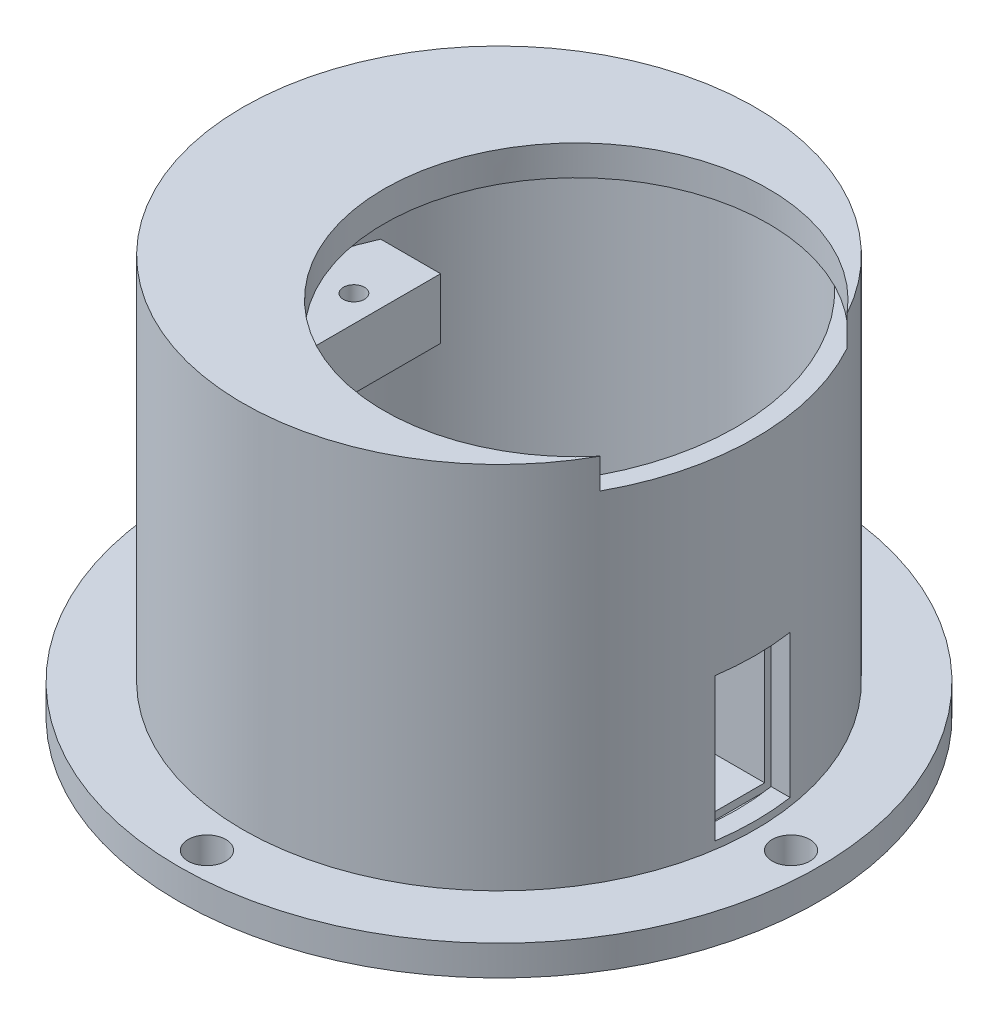
SolidWorks part; units mm, degrees
ref_plane "Front Plane" through (0, 0, 0) normal (0, 0, 1) x (1, 0, 0)
ref_plane "Top Plane" through (0, 0, 0) normal (0, 1, 0) x (1, 0, 0)
ref_plane "Right Plane" through (0, 0, 0) normal (1, 0, 0) x (0, 0, -1)
sketch "Sketch1" plane through (0, 0, 0) normal (0, 1, 0) x (1, 0, 0)
  circle A0 centre (0, 0) radius 30
  circle A1 centre (0, 0) radius 42.5
  dimension "D1" = 60
  dimension "D2" = 85
extrude "Boss-Extrude1" add sketch "Sketch1" along normal blind 4
sketch "Sketch2" plane through (0, 4, 0) normal (0, 1, 0) x (1, 0, 0)
  circle A3 centre (0, 0) radius 34
  circle A6 centre (0, 0) radius 31.5
  dimension "D1" = 63
extrude "Boss-Extrude2" add sketch "Sketch2" along normal blind 45
sketch "Sketch3" plane through (0, 0, 0) normal (0, 0, 1) x (1, 0, 0)
  line L0 (0, 0) -> (0, 49) construction
  line L1 (34, 49) -> (-34, 49) construction
  line L2 (-42.5, 0) -> (42.5, 0) construction
  line L3 (22.25, 0) -> (30.25, 0)
  line L4 (22.25, 0) -> (22.25, 34)
  line L5 (22.25, 34) -> (30.25, 34)
  line L6 (30.25, 0) -> (30.25, 34)
  line L8 (42.5, 4) -> (-42.5, 4) construction
  line L9 (-31.25, 34) -> (-20.75, 34)
  line L10 (-31.25, 34) -> (-31.25, 26)
  line L11 (-31.25, 26) -> (-20.75, 26)
  line L12 (-20.75, 34) -> (-20.75, 26)
  point P17 (0, 0)
  point P19 (-34, 38)
  dimension "D1" = 8
  dimension "D2" = 22.25
  dimension "D3" = 30
  dimension "D4" = 22
  dimension "D5" = 8
  dimension "D6" = 20.75
  dimension "D7" = 10.5
extrude "Boss-Extrude3" add sketch "Sketch3" along normal mid plane 26
sketch "Sketch4" plane through (22.25, 0, 0) normal (-1, 0, 0) x (0, 0, 1)
  line L0 (0, 0) -> (0, 34) construction
  line L1 (13, 0) -> (-13, 0) construction
  line L2 (13, 34) -> (-13, 34) construction
  line L4 (-5, 5) -> (5, 5)
  line L5 (-5, 5) -> (-5, 24)
  line L6 (-5, 24) -> (5, 24)
  line L7 (5, 5) -> (5, 24)
  line L8 (-5, 5) -> (5, 24) construction
  line L9 (-5, 24) -> (5, 5) construction
  point P6 (0, 14.5)
  dimension "D1" = 5
  dimension "D2" = 10
  dimension "D3" = 10
extrude "Cut-Extrude1" cut sketch "Sketch4" against normal through all
sketch "Sketch6" plane through (0, 34, 0) normal (0, 1, 0) x (1, 0, 0)
  line L0 (-24.25, 13) -> (-24.25, -13) construction
  line L1 (-20.75, 13) -> (-28.6923, 13) construction
  line L2 (-20.75, -13) -> (-28.6923, -13) construction
  line L3 (-20.75, -13) -> (-20.75, 13) construction
  line L4 (-24.25, 0) -> (24.75, 0) construction
  line L6 (24.75, -13) -> (24.75, 13)
  line L7 (28.6923, 13) -> (22.25, 13) construction
  circle A0 centre (-24.25, -5) radius 1.4
  circle A1 centre (24.75, -5) radius 1.4
  circle A2 centre (24.75, 5) radius 1.4
  circle A3 centre (-24.25, 5) radius 1.4
  point P15 (24.75, 0)
  dimension "D3" = 2.8
  dimension "D1" = 3.5
  dimension "D2" = 49
  dimension "D4" = 5
extrude "Cut-Extrude3" cut sketch "Sketch6" against normal blind 7.2 contours A3 | A2 | A1 | A0
sketch "Sketch8" plane through (0, 4, 0) normal (0, 1, 0) x (1, 0, 0)
  circle A0 centre (0, 0) radius 38.75 construction
  circle A1 centre (-38.75, 0) radius 2.5
  circle A2 centre (0, 38.75) radius 2.5
  circle A3 centre (38.75, 0) radius 2.5
  circle A4 centre (0, -38.75) radius 2.5
  point P13 (0, 0)
  dimension "D1" = 77.5
  dimension "D2" = 5
  dimension "D3" = 4
extrude "Cut-Extrude4" cut sketch "Sketch8" against normal up to surface (4 mm away) up to face at (10.3843, 0, 0)
sketch "Sketch9" plane through (0, 49, 0) normal (0, 1, 0) x (1, 0, 0)
  circle A11 centre (10.25, 0) radius 25.5
  arc A12 (29.7957, 16.3773) -> (29.7957, -16.3773) centre (10.25, 0) ccw
  circle A14 centre (0, 0) radius 34
  arc A15 (29.7957, 16.3773) -> (29.7957, -16.3773) centre (0, 0) ccw
  dimension "D1" = 0.5
  dimension "D2" = 2.5
extrude "Boss-Extrude4" add sketch "Sketch9" along normal blind 4
